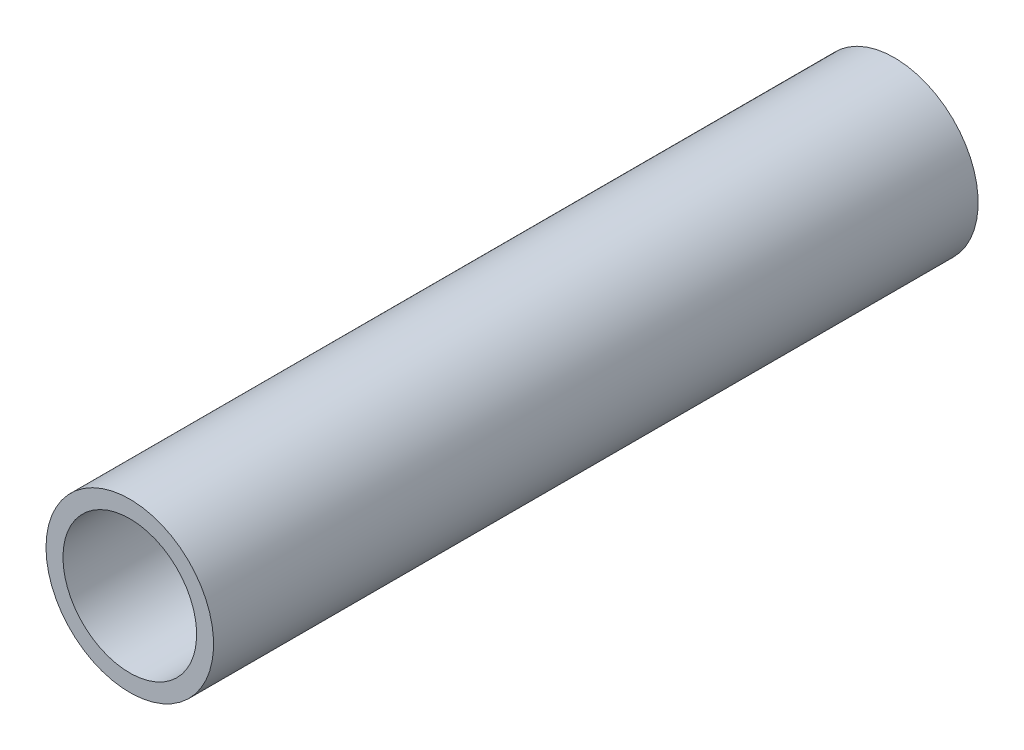
SolidWorks part; units mm, degrees
ref_plane "Front Plane" through (0, 0, 0) normal (0, 0, 1) x (1, 0, 0)
ref_plane "Top Plane" through (0, 0, 0) normal (0, 1, 0) x (1, 0, 0)
ref_plane "Right Plane" through (0, 0, 0) normal (1, 0, 0) x (0, 0, -1)
sketch "Sketch1" plane through (0, 0, 0) normal (0, 0, 1) x (1, 0, 0)
  circle A0 centre (0, 0) radius 16.7005
  dimension "Pipe OD" = 33.401
extrude "Extrude-Thin1" add sketch "Sketch1" along normal mid plane 152.4 thin thin type one direction reverse wall 3.3782
